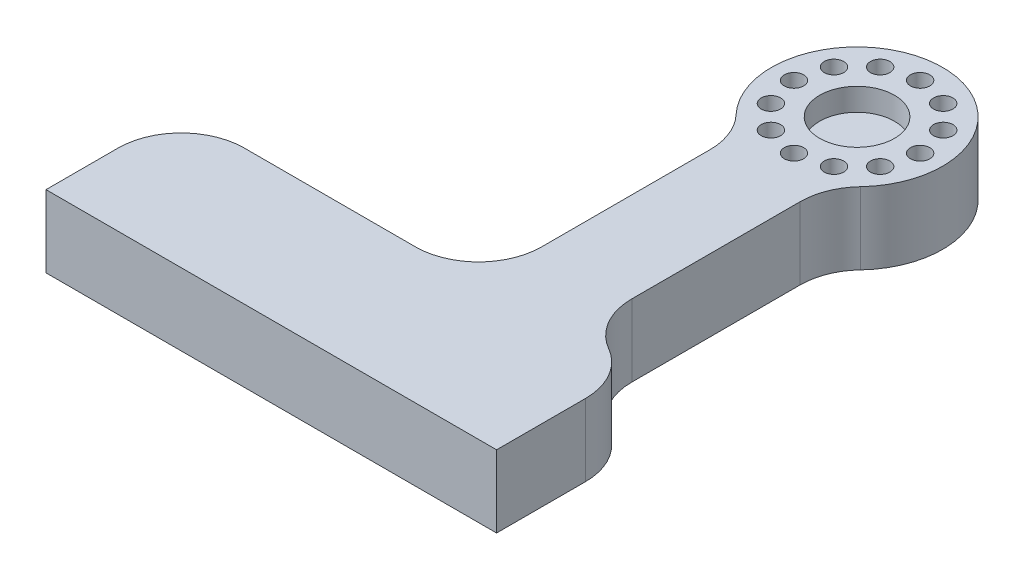
SolidWorks part; units mm, degrees
other "Markup1"
sketch "Sketch3" plane through (-38, 10, 52) normal (-0.2608, 0.9654, 0.0051) x (0.9654, 0.2608, -0.003)
ref_plane "Front Plane" through (0, 0, 0) normal (0, 0, 1) x (1, 0, 0)
ref_plane "Top Plane" through (0, 0, 0) normal (0, 1, 0) x (1, 0, 0)
ref_plane "Right Plane" through (0, 0, 0) normal (1, 0, 0) x (0, 0, -1)
sketch "Sketch1" plane through (0, 0, 0) normal (0, 1, 0) x (1, 0, 0)
  line L0 (9.5, 25.5876) -> (9.5, -14.2592) construction
  line L1 (-38, -52) -> (12, -52)
  line L2 (-38, -52) -> (-38, -37)
  line L3 (-38, -37) -> (12, -37)
  line L4 (12, -52) -> (12, -37)
  line L5 (-13, -37) -> (-13, -52) construction
  line L6 (-5, -37) -> (-5, 0)
  line L7 (-55, 0) -> (55, 0) construction
  line L8 (-5, 0) -> (5, 0)
  line L9 (5, 0) -> (5, -37)
  line L10 (0, 0) -> (0, -25.6078) construction
  circle A0 centre (0, 0) radius 9.5
  circle A1 centre (0, 0) radius 7 construction
  circle A2 centre (0, 7) radius 1.075
  circle A3 centre (3.5, 6.0622) radius 1.075
  circle A4 centre (6.0622, 3.5) radius 1.075
  circle A5 centre (7, 0) radius 1.075
  circle A6 centre (6.0622, -3.5) radius 1.075
  circle A7 centre (3.5, -6.0622) radius 1.075
  circle A8 centre (0, -7) radius 1.075
  circle A9 centre (-3.5, -6.0622) radius 1.075
  circle A10 centre (-6.0622, -3.5) radius 1.075
  circle A11 centre (-7, 0) radius 1.075
  circle A12 centre (-6.0622, 3.5) radius 1.075
  circle A13 centre (-3.5, 6.0622) radius 1.075
  point P31 (0, 0)
  dimension "D1" = 19
  dimension "D2" = 14
  dimension "D3" = 2.15
  dimension "D5" = 50
  dimension "D6" = 22.5
  dimension "D7" = 10
  dimension "D8" = 15
  dimension "D9" = 37
  dimension "D4" = 12
extrude "Boss-Extrude1" add sketch "Sketch1" along normal blind 8 contours A0 L6 L3 L9 | A10 L6 A0 L9 A6 L8 A9 A8 A7 | A10 L6 L8 L9 A6 A0 A13 A12 A11 A5 A4 A3 A2 | L1 L4 L3 L2 region at (-13, 0, 44.5) region at (0, 0, 23.0174) region at (0, 0, -2.1199) region at (0, 0, 4.2777)
sketch "Sketch2" plane through (0, 8, 0) normal (0, 1, 0) x (1, 0, 0)
  circle A0 centre (0, 0) radius 4.15
  dimension "D1" = 8.3
extrude "Cut-Extrude1" cut sketch "Sketch2" against normal blind 2.5
fillet "Fillet1" radius 7 1 edges at (5, 4, 37)
fillet "Fillet2" radius 7 1 edges at (-5, 4, 37)
fillet "Fillet3" radius 7 2 edges at (-5, 4, 8.0777) (5, 4, 8.0777)
fillet "Fillet4" radius 7 1 edges at (12, 4, 37)
fillet "Fillet5" radius 7 1 edges at (-38, 4, 37)
